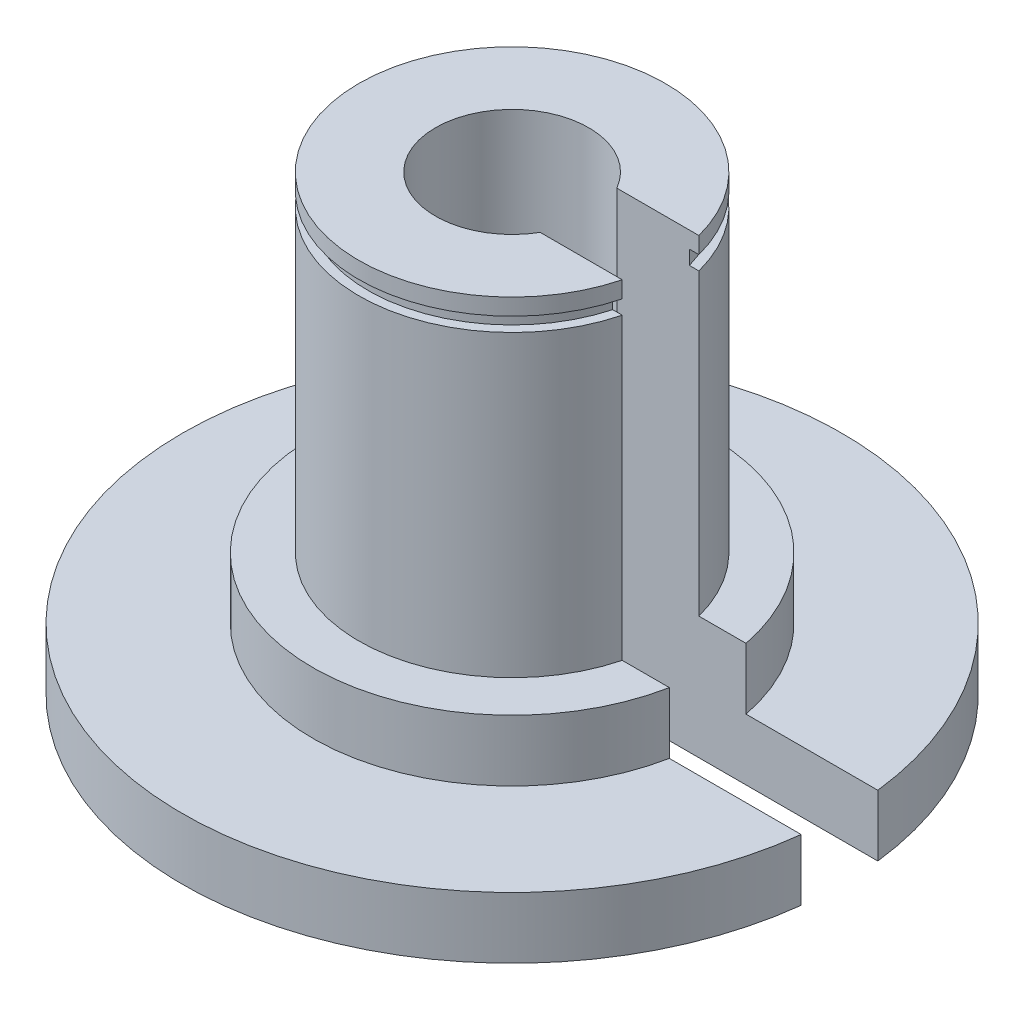
SolidWorks part; units mm, degrees
material "6061-T6 (SS)"
ref_plane "Front Plane" through (0, 0, 0) normal (0, 0, 1) x (1, 0, 0)
ref_plane "Top Plane" through (0, 0, 0) normal (0, 1, 0) x (1, 0, 0)
ref_plane "Right Plane" through (0, 0, 0) normal (1, 0, 0) x (0, 0, -1)
sketch "Sketch1" plane through (0, 0, 0) normal (0, 1, 0) x (1, 0, 0)
  circle A0 centre (0, 0) radius 27.305
  circle A1 centre (0, 0) radius 4.5466
  dimension "D1" = 54.61
  dimension "D2" = 9.0932
extrude "Boss-Extrude1" add sketch "Sketch1" along normal blind 50.8
sketch "Sketch2" plane through (0, 50.8, 0) normal (0, 1, 0) x (1, 0, 0)
  circle A0 centre (0, 0) radius 6.35
  dimension "D1" = 12.7
extrude "Cut-Extrude1" cut sketch "Sketch2" against normal blind 44.45
sketch "Sketch3" plane through (0, 50.8, 0) normal (0, 1, 0) x (1, 0, 0)
  circle A0 centre (0, 0) radius 12.7
  dimension "D1" = 25.4
extrude "Cut-Extrude2" cut sketch "Sketch3" against normal blind 44.45 flip side to cut
ref_plane "Plane6" through (0, 37.465, 0) normal (0, 1, 0) x (-1, 0, 0)
ref_plane "Plane1" through (0, 17.4625, 0) normal (0, 1, 0) x (-1, 0, 0)
sketch "Sketch10" plane through (0, 0, 0) normal (0, -1, 0) x (1, 0, 0)
  line L1 (2.4998, -3.175) -> (33.1793, -3.175)
  line L2 (2.4998, -3.175) -> (2.4998, 3.175)
  line L3 (2.4998, 3.175) -> (33.1793, 3.175)
  line L4 (33.1793, -3.175) -> (33.1793, 3.175)
  dimension "D1" = 6.35
  dimension "D2" = 3.175
extrude "Cut-Extrude7" cut sketch "Sketch10" against normal blind 6.35
ref_plane "Plane4" through (0, 34.925, 0) normal (0, 1, 0) x (-1, 0, 0)
sketch "Sketch13" plane through (0, 34.925, 0) normal (0, 1, 0) x (-1, 0, 0)
  circle A3 centre (0, 0) radius 11.938
  dimension "D1" = 23.876
extrude "Cut-Extrude9" cut sketch "Sketch13" along normal blind 1.1684 flip side to cut
ref_plane "Plane5" through (0, 23.8125, 0) normal (0, 1, 0) x (-1, 0, 0)
sketch "Sketch16" plane through (0, 37.465, 0) normal (0, 1, 0) x (-1, 0, 0)
  circle A0 centre (0, 0) radius 46.0824
extrude "Cut-Extrude11" cut sketch "Sketch16" along normal through all
sketch "Sketch18" plane through (0, 6.35, 0) normal (0, 1, 0) x (1, 0, 0)
  circle A2 centre (0, 0) radius 16.51
  circle A3 centre (0, 0) radius 12.7
  circle A4 centre (0, 0) radius 12.7
  dimension "D1" = 0
  dimension "D2" = 3.81
extrude "Boss-Extrude4" add sketch "Sketch18" along normal blind 3.81
sketch "Sketch19" plane through (0, 6.35, 0) normal (0, 1, 0) x (1, 0, 0)
  circle A2 centre (0, 0) radius 16.51
  circle A3 centre (0, 0) radius 16.51
  dimension "D1" = 0
extrude "Cut-Extrude12" cut sketch "Sketch19" against normal blind 1.27 flip side to cut
extrude "Cut-Extrude13" cut sketch "Sketch10<2>" against normal through all
sketch "Sketch10<2>" plane through (0, 0, 0) normal (0, -1, 0) x (1, 0, 0) same geometry as "Sketch10"
